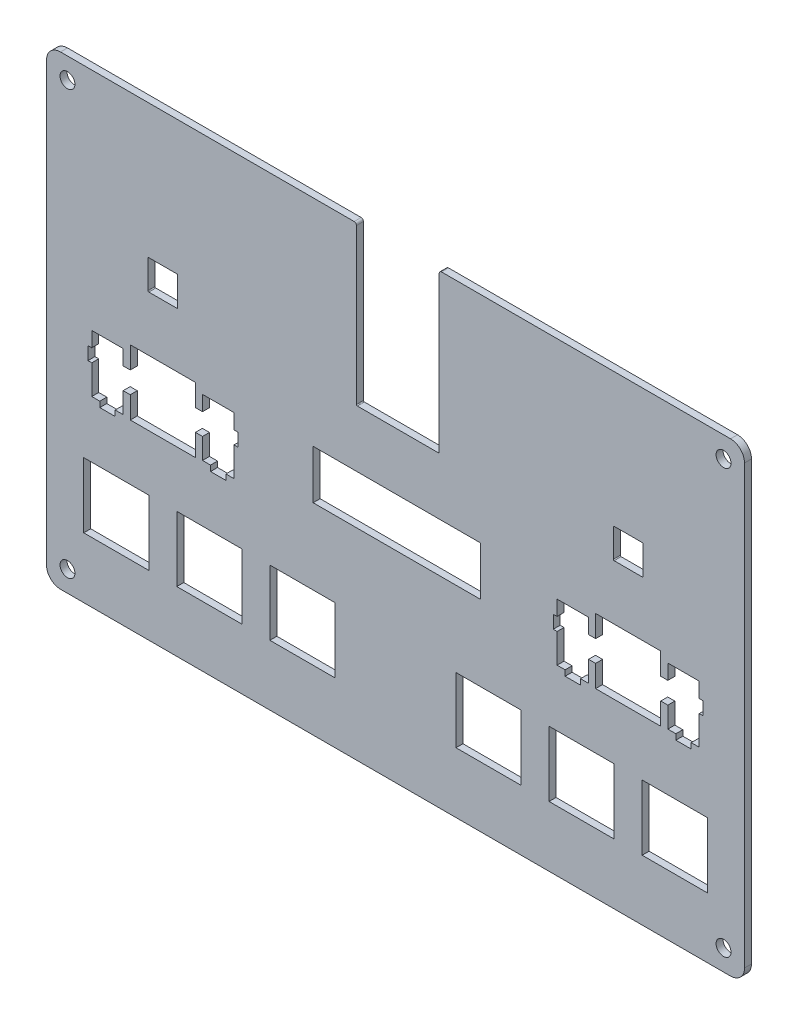
SolidWorks part; units mm, degrees
ref_plane "前视基准面" through (0, 0, 0) normal (0, 0, 1) x (1, 0, 0)
ref_plane "上视基准面" through (0, 0, 0) normal (0, 1, 0) x (1, 0, 0)
ref_plane "右视基准面" through (0, 0, 0) normal (1, 0, 0) x (0, 0, -1)
sketch "Model" plane through (0, 0, 0) normal (0, 0, 1) x (1, 0, 0)
  line L0 (3, 0) -> (147, 0)
  line L1 (150, 3) -> (150, 97)
  line L2 (0, 3) -> (0, 97)
  line L3 (66.61, 66.2) -> (66.61, 99.5)
  line L4 (3, 100) -> (66.11, 100)
  line L5 (84.89, 100) -> (147, 100)
  line L6 (66.81, 66) -> (84.19, 66)
  line L7 (93.3, 43.25) -> (57.3, 43.25)
  line L8 (8, 27) -> (22, 27)
  line L9 (22, 13) -> (22, 27)
  line L10 (8, 13) -> (8, 27)
  line L11 (8, 13) -> (22, 13)
  line L12 (28, 13) -> (28, 27)
  line L13 (42, 13) -> (42, 27)
  line L14 (28, 27) -> (42, 27)
  line L15 (28, 13) -> (42, 13)
  line L16 (48, 13) -> (48, 27)
  line L17 (62, 13) -> (62, 27)
  line L18 (48, 27) -> (62, 27)
  line L19 (48, 13) -> (62, 13)
  line L20 (88, 27) -> (102, 27)
  line L21 (88, 13) -> (102, 13)
  line L22 (88, 13) -> (88, 27)
  line L23 (102, 13) -> (102, 27)
  line L24 (108, 27) -> (122, 27)
  line L25 (108, 13) -> (122, 13)
  line L26 (122, 13) -> (122, 27)
  line L27 (108, 13) -> (108, 27)
  line L28 (128, 27) -> (142, 27)
  line L29 (128, 13) -> (142, 13)
  line L30 (142, 13) -> (142, 27)
  line L31 (128, 13) -> (128, 27)
  line L32 (57.3, 53.75) -> (93.3, 53.75)
  line L33 (128, 71.2) -> (122, 71.2)
  line L34 (121.8, 71) -> (121.8013, 65)
  line L35 (122.0013, 64.8) -> (128.0013, 64.8)
  line L36 (128.2013, 65) -> (128.2, 71)
  line L37 (25.0013, 64.8) -> (24.9987, 64.8)
  line L38 (28, 71.2) -> (22, 71.2)
  line L39 (22.0013, 64.8) -> (28.0013, 64.8)
  line L40 (28.2013, 65) -> (28.2, 71)
  line L41 (84.39, 99.5) -> (84.39, 66.2)
  line L42 (57.3, 53.75) -> (57.3, 43.25)
  line L43 (93.3, 53.75) -> (93.3, 43.25)
  line L44 (18, 52.9994) -> (18, 48.299)
  line L45 (18, 48.299) -> (16.4745, 48.299)
  line L46 (16.4745, 48.299) -> (16.4745, 51.5292)
  line L47 (16.4745, 51.5292) -> (9.7249, 51.5292)
  line L48 (9.7249, 51.5292) -> (9.7249, 48.299)
  line L49 (9.7249, 48.299) -> (8.8994, 48.299)
  line L50 (8.8994, 48.299) -> (8.8994, 45.5002)
  line L51 (8.8994, 45.5002) -> (9.7249, 45.5002)
  line L52 (9.7249, 45.5002) -> (9.7249, 39.2302)
  line L53 (9.7249, 39.2302) -> (11.4502, 39.2302)
  line L54 (11.4502, 39.2302) -> (11.4502, 38.0299)
  line L55 (11.4502, 38.0299) -> (14.7492, 38.0299)
  line L56 (14.7492, 38.0299) -> (14.7492, 39.2302)
  line L57 (14.7492, 39.2302) -> (16.4745, 39.2302)
  line L58 (16.4745, 39.2302) -> (16.4745, 43.6991)
  line L59 (16.4745, 43.6991) -> (18, 43.6991)
  line L60 (18, 43.6991) -> (18, 39)
  line L61 (18, 39) -> (31.9995, 39)
  line L62 (31.9995, 39) -> (31.9995, 43.6991)
  line L63 (31.9995, 43.6991) -> (33.525, 43.6991)
  line L64 (33.525, 43.6991) -> (33.525, 39.2302)
  line L65 (33.525, 39.2302) -> (35.2489, 39.2302)
  line L66 (35.2489, 39.2302) -> (35.2489, 38.0299)
  line L67 (35.2489, 38.0299) -> (38.5493, 38.0299)
  line L68 (38.5493, 38.0299) -> (38.5493, 39.2302)
  line L69 (38.5493, 39.2302) -> (40.2745, 39.2302)
  line L70 (40.2745, 39.2302) -> (40.2745, 45.5002)
  line L71 (40.2745, 45.5002) -> (41.1, 45.5002)
  line L72 (41.1, 45.5002) -> (41.1, 48.299)
  line L73 (41.1, 48.299) -> (40.2745, 48.299)
  line L74 (40.2745, 48.299) -> (40.2745, 51.5292)
  line L75 (40.2745, 51.5292) -> (33.525, 51.5292)
  line L76 (33.525, 51.5292) -> (33.525, 48.299)
  line L77 (33.525, 48.299) -> (31.9995, 48.299)
  line L78 (31.9995, 48.299) -> (31.9995, 52.9994)
  line L79 (31.9995, 52.9994) -> (18, 52.9994)
  line L80 (118, 52.9994) -> (118, 48.299)
  line L81 (118, 48.299) -> (116.4745, 48.299)
  line L82 (116.4745, 48.299) -> (116.4745, 51.5292)
  line L83 (116.4745, 51.5292) -> (109.7249, 51.5292)
  line L84 (109.7249, 51.5292) -> (109.7249, 48.299)
  line L85 (109.7249, 48.299) -> (108.8994, 48.299)
  line L86 (108.8994, 48.299) -> (108.8994, 45.5002)
  line L87 (108.8994, 45.5002) -> (109.7249, 45.5002)
  line L88 (109.7249, 45.5002) -> (109.7249, 39.2302)
  line L89 (109.7249, 39.2302) -> (111.4502, 39.2302)
  line L90 (111.4502, 39.2302) -> (111.4502, 38.0299)
  line L91 (111.4502, 38.0299) -> (114.7492, 38.0299)
  line L92 (114.7492, 38.0299) -> (114.7492, 39.2302)
  line L93 (114.7492, 39.2302) -> (116.4745, 39.2302)
  line L94 (116.4745, 39.2302) -> (116.4745, 43.6991)
  line L95 (116.4745, 43.6991) -> (118, 43.6991)
  line L96 (118, 43.6991) -> (118, 39)
  line L97 (118, 39) -> (131.9995, 39)
  line L98 (131.9995, 39) -> (131.9995, 43.6991)
  line L99 (131.9995, 43.6991) -> (133.525, 43.6991)
  line L100 (133.525, 43.6991) -> (133.525, 39.2302)
  line L101 (133.525, 39.2302) -> (135.2489, 39.2302)
  line L102 (135.2489, 39.2302) -> (135.2489, 38.0299)
  line L103 (135.2489, 38.0299) -> (138.5493, 38.0299)
  line L104 (138.5493, 38.0299) -> (138.5493, 39.2302)
  line L105 (138.5493, 39.2302) -> (140.2745, 39.2302)
  line L106 (140.2745, 39.2302) -> (140.2745, 45.5002)
  line L107 (140.2745, 45.5002) -> (141.1, 45.5002)
  line L108 (141.1, 45.5002) -> (141.1, 48.299)
  line L109 (141.1, 48.299) -> (140.2745, 48.299)
  line L110 (140.2745, 48.299) -> (140.2745, 51.5292)
  line L111 (140.2745, 51.5292) -> (133.525, 51.5292)
  line L112 (133.525, 51.5292) -> (133.525, 48.299)
  line L113 (133.525, 48.299) -> (131.9995, 48.299)
  line L114 (131.9995, 48.299) -> (131.9995, 52.9994)
  line L115 (131.9995, 52.9994) -> (118, 52.9994)
  line L116 (21.8, 71) -> (21.8013, 65)
  arc A0 (147, 0) -> (150, 3) centre (147, 3) ccw
  arc A1 (0, 3) -> (3, 0) centre (3, 3) ccw
  arc A2 (150, 97) -> (147, 100) centre (147, 97) ccw
  arc A3 (3, 100) -> (0, 97) centre (3, 97) ccw
  circle A4 centre (4.5, 95.5) radius 1.6
  circle A5 centre (4.5, 4.5) radius 1.6
  arc A6 (66.61, 99.5) -> (66.11, 100) centre (66.11, 99.5) ccw
  arc A7 (84.89, 100) -> (84.39, 99.5) centre (84.89, 99.5) ccw
  arc A8 (66.61, 66.2) -> (66.81, 66) centre (66.81, 66.2) ccw
  arc A9 (84.19, 66) -> (84.39, 66.2) centre (84.19, 66.2) ccw
  circle A10 centre (145.5, 4.5) radius 1.6
  circle A11 centre (145.5, 95.5) radius 1.6
  arc A12 (122, 71.2) -> (121.8, 71) centre (122, 71) ccw
  arc A13 (121.8013, 65) -> (122.0013, 64.8) centre (122.0013, 65) ccw
  arc A14 (128.0013, 64.8) -> (128.2013, 65) centre (128.0013, 65) ccw
  arc A15 (128.2, 71) -> (128, 71.2) centre (128, 71) ccw
  arc A16 (24.9987, 64.8) -> (25.0013, 64.8) centre (25, 68) ccw
  arc A17 (22, 71.2) -> (21.8, 71) centre (22, 71) ccw
  arc A18 (28.0013, 64.8) -> (28.2013, 65) centre (28.0013, 65) ccw
  arc A19 (21.8013, 65) -> (22.0013, 64.8) centre (22.0013, 65) ccw
  arc A20 (28.2, 71) -> (28, 71.2) centre (28, 71) ccw
  point P59 (0, 0)
  point P60 (93.3, 42.8999)
  point P85 (57.3, 42.8094)
  point P86 (0, 0)
  point P159 (0, 0)
  point P162 (0, 0)
  point P163 (0, 0)
  point P164 (57.3, 53.184)
  point P168 (0, 0)
  point P169 (0, 0)
  point P170 (0, 0)
  point P171 (0, 0)
  point P172 (0, 0)
  point P173 (57.3, 43.3796)
  dimension "D1" = 10.5
extrude "凸台-拉伸1" add sketch "Model" along normal blind 1.5 contours A9 L6 A8 L3 A6 L4 A3 L2 A1 L0 A0 L1 A2 L5 A7 L41 A20 L40 A18 L39 L37 A19 L116 A17 L38 A15 L36 A14 L35 A13 L34 A12 L33 A11 A10 A5 A4 L115 L114 L113 L112 L111 L110 region at (2.1534, 2.1534, 0)
